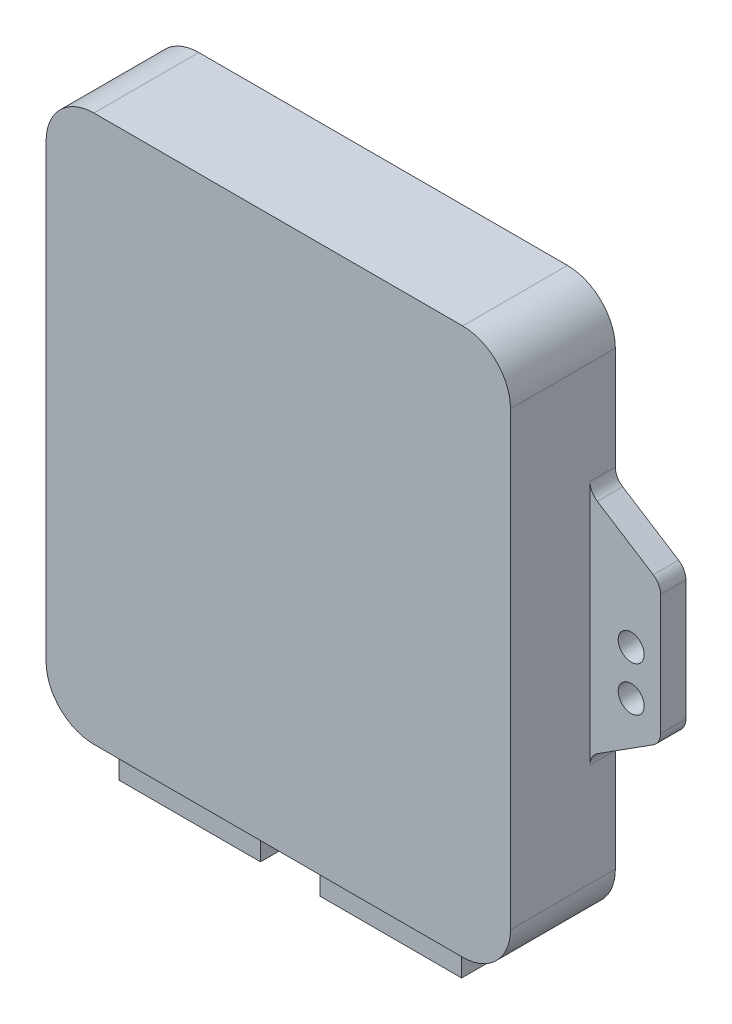
SolidWorks part; units mm, degrees
ref_plane "Front Plane" through (0, 0, 0) normal (0, 0, 1) x (1, 0, 0)
ref_plane "Top Plane" through (0, 0, 0) normal (0, 1, 0) x (1, 0, 0)
ref_plane "Right Plane" through (0, 0, 0) normal (1, 0, 0) x (0, 0, -1)
sketch "Sketch1" plane through (0, 0, 0) normal (0, 0, 1) x (1, 0, 0)
  line L1 (-29.125, 34.29) -> (29.125, 34.29)
  line L2 (-29.125, 34.29) -> (-29.125, -34.29)
  line L3 (-29.125, -34.29) -> (29.125, -34.29)
  line L4 (29.125, 34.29) -> (29.125, -34.29)
  line L5 (-29.125, 34.29) -> (29.125, -34.29) construction
  line L6 (-29.125, -34.29) -> (29.125, 34.29) construction
  point P0 (0, 0)
  dimension "D1" = 58.25
  dimension "D2" = 68.58
extrude "Boss-Extrude1" add sketch "Sketch1" along normal mid plane 13.15
fillet "Fillet1" radius 6 4 edges at (29.125, -34.29, 0) (-29.125, -34.29, 0) (29.125, 34.29, 0) (-29.125, 34.29, 0)
sketch "Sketch2" plane through (0, 0, -6.575) normal (0, 0, -1) x (-1, 0, 0)
  line L0 (-29.125, 14.29) -> (-37.975, 8.65)
  line L1 (-29.125, -28.29) -> (-29.125, 28.29) construction
  line L2 (-37.975, 8.65) -> (-37.975, -8.65)
  line L3 (-37.975, -8.65) -> (-29.125, -14.29)
  line L4 (-23.125, 34.29) -> (23.125, 34.29) construction
  line L5 (-29.125, 14.29) -> (-29.125, -14.29)
  point P4 (-37.975, 0)
  dimension "D1" = 20
  dimension "D2" = 8.85
  dimension "D3" = 17.3
extrude "Boss-Extrude2" add sketch "Sketch2" against normal blind 3.175
sketch "Sketch6" plane through (0, -34.29, 0) normal (0, -1, 0) x (1, 0, 0)
  line L0 (-29.125, -6.575) -> (-29.125, 6.575) construction
  line L1 (-21.505, 5.08) -> (-3.725, 5.08)
  line L2 (-21.505, 5.08) -> (-21.505, 0)
  line L3 (-21.505, 0) -> (-3.725, 0)
  line L4 (-3.725, 5.08) -> (-3.725, 0)
  line L5 (-21.505, 5.08) -> (-3.725, 0) construction
  line L6 (-21.505, 0) -> (-3.725, 5.08) construction
  point P0 (-12.615, 2.54)
  dimension "D1" = 5.08
  dimension "D2" = 17.78
  dimension "D3" = 7.62
extrude "Boss-Extrude3" add sketch "Sketch6" along normal blind 3.81
hole_wizard "#30 (0.1285) Diameter Hole1" positions "Sketch3" profile "Sketch4" hole size "#30" standard "ANSI Inch" end condition through all
sketch "Sketch3" plane through (0, 0, -3.4) normal (0, 0, 1) x (1, 0, 0)
  line L0 (-23.125, -34.29) -> (23.125, -34.29) construction
  point P0 (34.29, 0)
  point P2 (34.29, -5.588)
  dimension "D1" = 28.702
  dimension "D2" = 34.29
  dimension "D3" = 34.29
sketch "Sketch4" plane through (34.29, 0, -3.4) normal (1, 0, 0) x (0, -1, 0)
  line L0 (0, 0) -> (0, 3.175)
  line L1 (0, 3.175) -> (1.6319, 3.175)
  line L2 (1.6319, 3.175) -> (1.6319, 0)
  line L5 (1.6319, 0) -> (0, 0)
  line L11 (0, -6.35) -> (0, 107.95) construction
  dimension "Thru Hole Dia." = 3.2639
  dimension "Thru Hole Depth" = 3.175
mirror "Mirror1" about plane through (0, 0, 0) normal (1, 0, 0) of "Boss-Extrude3", "Boss-Extrude2", "#30 (0.1285) Diameter Hole1"
fillet "Fillet2" radius 2 8 edges at (29.125, 14.29, -4.9875) (37.975, 8.65, -4.9875) (37.975, -8.65, -4.9875) (29.125, -14.29, -4.9875) (-29.125, -14.29, -4.9875) (-37.975, -8.65, -4.9875) (-37.975, 8.65, -4.9875) (-29.125, 14.29, -4.9875)
sketch "Sketch5" plane through (0, 0, -3.4) normal (0, 0, 1) x (1, 0, 0)
  line L0 (-33.6169, -5.588) -> (-34.9631, -5.588) construction
  line L1 (-33.6169, -7.2072) -> (-34.9631, -7.2072)
  line L2 (-33.6169, -3.9688) -> (-34.9631, -3.9688)
  arc A0 (-33.6169, -7.2072) -> (-33.6169, -3.9688) centre (-33.6169, -5.588) ccw
  arc A1 (-34.9631, -3.9688) -> (-34.9631, -7.2072) centre (-34.9631, -5.588) ccw
  circle A2 centre (-34.29, -5.588) radius 1.632 construction
  point P2 (-34.29, -5.588)
  dimension "D2" = 1.6193
  dimension "D1" = 1.3462
extrude "Cut-Extrude1" cut sketch "Sketch5" against normal through all
equation "\"len\"= 58.25mm"
equation "\"D1@Sketch1\"=\"len\""
equation "\"D2@Sketch2\"=(75.95 - \"len\")/2"
